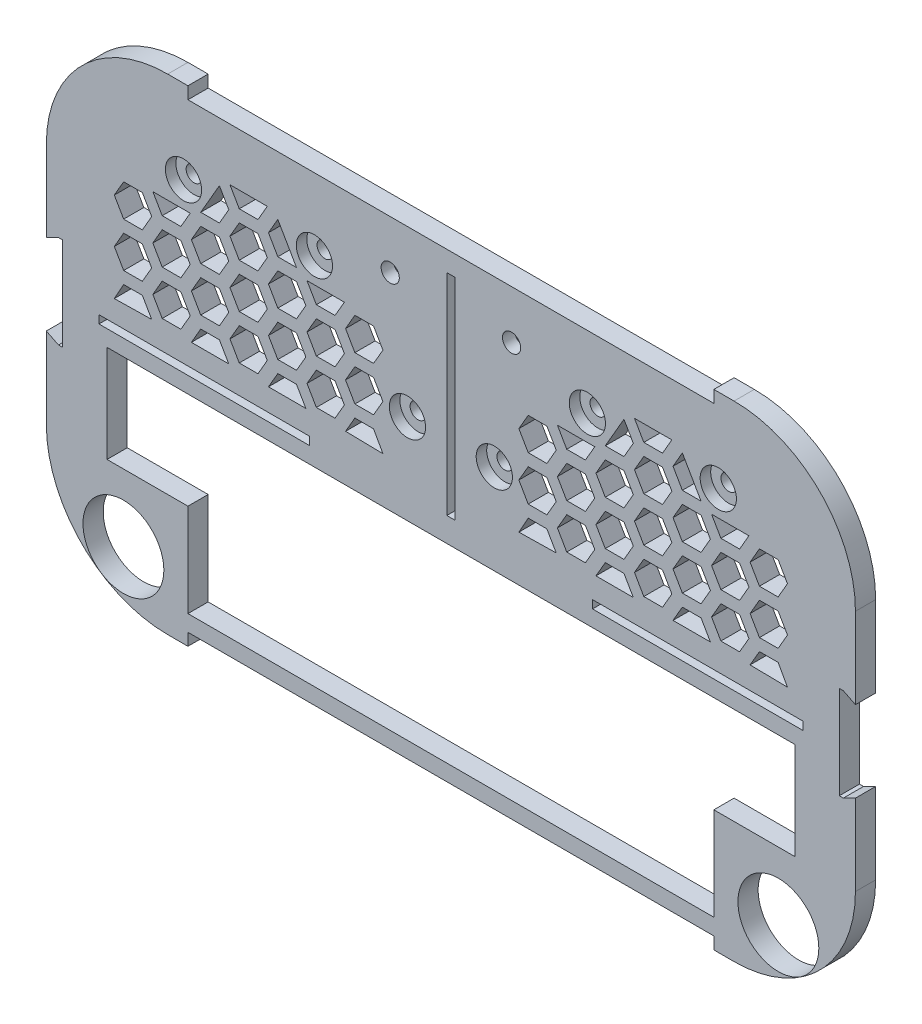
SolidWorks part; units mm, degrees
ref_plane "前视基准面" through (0, 0, 0) normal (0, 0, 1) x (1, 0, 0)
ref_plane "上视基准面" through (0, 0, 0) normal (0, 1, 0) x (1, 0, 0)
ref_plane "右视基准面" through (0, 0, 0) normal (1, 0, 0) x (0, 0, -1)
sketch "草图1" plane through (0, 0, 0) normal (0, 0, 1) x (1, 0, 0)
  line L1 (70, 60) -> (-70, 60)
  line L2 (-100, 30) -> (-100, -30)
  line L4 (70, -60) -> (-70, -60)
  line L5 (100, 30) -> (100, -30)
  arc A0 (-70, 60) -> (-100, 30) centre (-70, 30) ccw
  arc A1 (-70, -60) -> (-100, -30) centre (-70, -30) cw
  arc A2 (70, -60) -> (100, -30) centre (70, -30) ccw
  arc A3 (70, 60) -> (100, 30) centre (70, 30) cw
  point P12 (0, -60)
extrude "凸台-拉伸1" add sketch "草图1" along normal blind 5
sketch "草图2" plane through (0, 0, 0) normal (0, 0, 1) x (1, 0, 0)
  circle A0 centre (-80.95, 46.6721) radius 10
  circle A1 centre (80.95, 46.6721) radius 10
  circle A2 centre (80.95, -46.6721) radius 10
  circle A3 centre (-80.95, -46.6721) radius 10
extrude "孔" cut sketch "草图2" along normal blind 4 contours A1 | A0 region at (-80.95, 46.6721, 0) region at (80.95, 46.6721, 0)
extrude "穿孔" cut sketch "草图2<3>" along normal up to next contours A2 | A3 region at (80.95, -46.6721, 0) region at (-80.95, -46.6721, 0)
sketch "草图2<3>" plane through (0, 0, 0) normal (0, 0, 1) x (1, 0, 0) same geometry as "草图2"
sketch "草图3" plane through (0, 0, 0) normal (0, 0, 1) x (1, 0, 0)
  line L8 (-85, -6) -> (-85, -30)
  line L12 (-70, -30) -> (-65, -30)
  line L22 (-85, -30) -> (-70, -30)
  line L26 (85, -30) -> (70, -30)
  line L32 (70, -30) -> (65, -30)
  line L37 (-65, -30) -> (-65, -53)
  line L39 (65, -53) -> (65, -30)
  line L40 (-65, -60) -> (-65, -57)
  line L41 (-70, -60) -> (70, -60) construction
  line L42 (-65, -57) -> (65, -57)
  line L43 (65, -57) -> (65, -60)
  line L44 (-65, -60) -> (65, -60)
  line L50 (-100, -10) -> (-97, -11.5)
  line L53 (-100, 10) -> (-100, -10)
  line L55 (-85, -6) -> (85, -6)
  line L56 (85, -6) -> (85, -30)
  line L88 (65, -53) -> (-65, -53)
  line L89 (87, 0) -> (87, -2)
  line L90 (87, -2) -> (35, -2)
  line L92 (87, 0) -> (37, 0)
  line L96 (35, 0) -> (35, -2)
  line L105 (-35, 0) -> (-35, -2)
  line L109 (-87, 0) -> (-37, 0)
  line L110 (-87, -2) -> (-35, -2)
  line L111 (-87, 0) -> (-87, -2)
  line L112 (97, 11.5) -> (96, 11.5)
  line L114 (-97, 11.5) -> (-100, 10)
  line L115 (97, 11.5) -> (100, 10)
  line L118 (100, 10) -> (100, -10)
  line L119 (100, -10) -> (97, -11.5)
  line L120 (96, 11.5) -> (96, -11.5)
  line L121 (96, -11.5) -> (97, -11.5)
  line L122 (-97, 11.5) -> (-96, 11.5)
  line L123 (-96, 11.5) -> (-96, -11.5)
  line L124 (-96, -11.5) -> (-97, -11.5)
  line L125 (0, 0) -> (-1, 0)
  line L126 (-1, 0) -> (-1, 50)
  line L128 (1, 50) -> (1, 0)
  line L129 (1, 0) -> (0, 0)
  line L130 (-1, 50) -> (-1, 52)
  line L131 (-1, 52) -> (1, 52)
  line L132 (1, 52) -> (1, 50)
  line L133 (-37, 0) -> (-35, 0)
  line L134 (35, 0) -> (37, 0)
  line L135 (-65, 57) -> (-65, 60)
  line L136 (-65, 57) -> (65, 57)
  line L138 (65, 57) -> (65, 60)
  line L139 (65, 60) -> (-65, 60)
extrude "切除-拉伸4" cut sketch "草图3" along normal up to next
hole_wizard "M3.5 六角头机械螺钉的柱形沉头孔1" positions "3D草图1" profile "草图4" counterbore size "M3.5" standard "ANSI Metric" end condition through all
sketch3d "3D草图1"
  point P31 (-66.0951, 39.3344, 5)
  point P33 (-33.736, 39.2649, 5)
  point P35 (-10.7334, 16.264, 5)
  point P78 (33.736, 39.2649, 5)
  point P80 (10.7334, 16.264, 5)
  point P82 (66.0951, 39.3344, 5)
sketch "草图4" plane through (-66.0951, 39.3344, 5) normal (1, 0, 0) x (0, -1, 0)
  line L0 (0, 0) -> (0, 5)
  line L1 (0, 5) -> (1.95, 5)
  line L3 (1.95, 5) -> (1.95, 2.6)
  line L4 (1.95, 2.6) -> (4.48, 2.6)
  line L5 (4.48, 2.6) -> (4.48, 0)
  line L7 (4.48, 0) -> (0, 0)
  line L11 (0, -6.35) -> (0, 107.95) construction
  dimension "通孔孔直径" = 3.9
  dimension "通孔孔深度" = 5
  dimension "柱形沉头孔直径" = 8.96
  dimension "柱形沉头孔深度" = 2.6
sketch "草图5" plane through (0, 0, 0) normal (0, 0, 1) x (1, 0, 0)
  line L4 (-35.8549, 5.5) -> (-38.1643, 9.5)
  line L6 (-38.1643, 9.5) -> (-42.7831, 9.5)
  line L13 (-42.7831, 9.5) -> (-45.0925, 5.5)
  line L17 (-26.3286, 11) -> (-28.638, 15)
  line L18 (-28.638, 15) -> (-33.2568, 15)
  line L19 (-33.2568, 15) -> (-35.5662, 11)
  line L20 (-35.5662, 11) -> (-33.2568, 7)
  line L21 (-33.2568, 7) -> (-28.638, 7)
  line L22 (-28.638, 7) -> (-26.3286, 11)
  line L23 (-16.8024, 16.5) -> (-19.1118, 20.5)
  line L24 (-19.1118, 20.5) -> (-23.7306, 20.5)
  line L25 (-23.7306, 20.5) -> (-26.04, 16.5)
  line L26 (-26.04, 16.5) -> (-23.7306, 12.5)
  line L27 (-23.7306, 12.5) -> (-19.1118, 12.5)
  line L28 (-19.1118, 12.5) -> (-16.8024, 16.5)
  line L29 (-35.8549, 16.5) -> (-38.1643, 20.5)
  line L30 (-38.1643, 20.5) -> (-42.7831, 20.5)
  line L31 (-42.7831, 20.5) -> (-45.0925, 16.5)
  line L32 (-45.0925, 16.5) -> (-42.7831, 12.5)
  line L33 (-42.7831, 12.5) -> (-38.1643, 12.5)
  line L34 (-38.1643, 12.5) -> (-35.8549, 16.5)
  line L35 (-26.3286, 22) -> (-28.638, 26)
  line L36 (-28.638, 26) -> (-33.2568, 26)
  line L37 (-33.2568, 26) -> (-35.5662, 22)
  line L38 (-35.5662, 22) -> (-33.2568, 18)
  line L39 (-33.2568, 18) -> (-28.638, 18)
  line L40 (-28.638, 18) -> (-26.3286, 22)
  line L41 (-16.8024, 27.5) -> (-19.1118, 31.5)
  line L42 (-19.1118, 31.5) -> (-23.7306, 31.5)
  line L43 (-23.7306, 31.5) -> (-26.04, 27.5)
  line L44 (-26.04, 27.5) -> (-23.7306, 23.5)
  line L45 (-23.7306, 23.5) -> (-19.1118, 23.5)
  line L46 (-19.1118, 23.5) -> (-16.8024, 27.5)
  line L47 (-35.8549, 27.5) -> (-38.1643, 31.5)
  line L48 (-38.1643, 31.5) -> (-42.7831, 31.5)
  line L49 (-42.7831, 31.5) -> (-45.0925, 27.5)
  line L50 (-45.0925, 27.5) -> (-42.7831, 23.5)
  line L51 (-42.7831, 23.5) -> (-38.1643, 23.5)
  line L52 (-38.1643, 23.5) -> (-35.8549, 27.5)
  line L56 (-35.5662, 33) -> (-33.2568, 29)
  line L57 (-33.2568, 29) -> (-28.638, 29)
  line L58 (-28.638, 29) -> (-26.3286, 33)
  line L67 (-42.7831, 42.5) -> (-45.0925, 38.5)
  line L68 (-45.0925, 38.5) -> (-42.7831, 34.5)
  line L69 (-42.7831, 34.5) -> (-38.1643, 34.5)
  line L83 (-45.3812, 11) -> (-47.6906, 15)
  line L84 (-47.6906, 15) -> (-52.3094, 15)
  line L85 (-52.3094, 15) -> (-54.6188, 11)
  line L86 (-54.6188, 11) -> (-52.3094, 7)
  line L87 (-52.3094, 7) -> (-47.6906, 7)
  line L88 (-47.6906, 7) -> (-45.3812, 11)
  line L89 (-45.3812, 22) -> (-47.6906, 26)
  line L90 (-47.6906, 26) -> (-52.3094, 26)
  line L91 (-52.3094, 26) -> (-54.6188, 22)
  line L92 (-54.6188, 22) -> (-52.3094, 18)
  line L93 (-52.3094, 18) -> (-47.6906, 18)
  line L94 (-47.6906, 18) -> (-45.3812, 22)
  line L95 (-45.3812, 33) -> (-47.6906, 37)
  line L96 (-47.6906, 37) -> (-52.3094, 37)
  line L97 (-52.3094, 37) -> (-54.6188, 33)
  line L98 (-54.6188, 33) -> (-52.3094, 29)
  line L99 (-52.3094, 29) -> (-47.6906, 29)
  line L100 (-47.6906, 29) -> (-45.3812, 33)
  line L125 (-42.7831, 42.5) -> (-38.1643, 34.5)
  line L126 (-35.5662, 33) -> (-26.3286, 33)
  line L127 (-45.0925, 5.5) -> (-35.8549, 5.5)
  line L129 (-54.9075, 5.5) -> (-64.1451, 5.5)
  line L130 (-64.4338, 33) -> (-73.6714, 33)
  line L131 (-57.2169, 42.5) -> (-61.8357, 34.5)
  line L132 (-57.2169, 34.5) -> (-61.8357, 34.5)
  line L133 (-54.9075, 38.5) -> (-57.2169, 34.5)
  line L134 (-57.2169, 42.5) -> (-54.9075, 38.5)
  line L135 (-71.362, 29) -> (-73.6714, 33)
  line L136 (-66.7432, 29) -> (-71.362, 29)
  line L137 (-64.4338, 33) -> (-66.7432, 29)
  line L138 (-61.8357, 23.5) -> (-64.1451, 27.5)
  line L139 (-57.2169, 23.5) -> (-61.8357, 23.5)
  line L140 (-54.9075, 27.5) -> (-57.2169, 23.5)
  line L141 (-57.2169, 31.5) -> (-54.9075, 27.5)
  line L142 (-61.8357, 31.5) -> (-57.2169, 31.5)
  line L143 (-64.1451, 27.5) -> (-61.8357, 31.5)
  line L144 (-80.8882, 23.5) -> (-83.1976, 27.5)
  line L145 (-76.2694, 23.5) -> (-80.8882, 23.5)
  line L146 (-73.96, 27.5) -> (-76.2694, 23.5)
  line L147 (-76.2694, 31.5) -> (-73.96, 27.5)
  line L148 (-80.8882, 31.5) -> (-76.2694, 31.5)
  line L149 (-83.1976, 27.5) -> (-80.8882, 31.5)
  line L150 (-71.362, 18) -> (-73.6714, 22)
  line L151 (-66.7432, 18) -> (-71.362, 18)
  line L152 (-64.4338, 22) -> (-66.7432, 18)
  line L153 (-66.7432, 26) -> (-64.4338, 22)
  line L154 (-71.362, 26) -> (-66.7432, 26)
  line L155 (-73.6714, 22) -> (-71.362, 26)
  line L156 (-61.8357, 12.5) -> (-64.1451, 16.5)
  line L157 (-57.2169, 12.5) -> (-61.8357, 12.5)
  line L158 (-54.9075, 16.5) -> (-57.2169, 12.5)
  line L159 (-57.2169, 20.5) -> (-54.9075, 16.5)
  line L160 (-61.8357, 20.5) -> (-57.2169, 20.5)
  line L161 (-64.1451, 16.5) -> (-61.8357, 20.5)
  line L162 (-80.8882, 12.5) -> (-83.1976, 16.5)
  line L163 (-76.2694, 12.5) -> (-80.8882, 12.5)
  line L164 (-73.96, 16.5) -> (-76.2694, 12.5)
  line L165 (-76.2694, 20.5) -> (-73.96, 16.5)
  line L166 (-80.8882, 20.5) -> (-76.2694, 20.5)
  line L167 (-83.1976, 16.5) -> (-80.8882, 20.5)
  line L168 (-71.362, 7) -> (-73.6714, 11)
  line L169 (-66.7432, 7) -> (-71.362, 7)
  line L170 (-64.4338, 11) -> (-66.7432, 7)
  line L171 (-66.7432, 15) -> (-64.4338, 11)
  line L172 (-71.362, 15) -> (-66.7432, 15)
  line L173 (-73.6714, 11) -> (-71.362, 15)
  line L174 (-57.2169, 9.5) -> (-54.9075, 5.5)
  line L175 (-61.8357, 9.5) -> (-57.2169, 9.5)
  line L176 (-64.1451, 5.5) -> (-61.8357, 9.5)
  line L181 (-52.3094, 40) -> (-47.6906, 40)
  line L184 (-52.3094, 44) -> (-54.6188, 44)
  line L185 (-54.6188, 44) -> (-52.3094, 40)
  line L186 (-52.3094, 44) -> (-45.3812, 44)
  line L187 (-45.3812, 44) -> (-47.6906, 40)
  line L188 (-21.4212, 9.5) -> (-23.7306, 9.5)
  line L191 (-26.04, 5.5) -> (-23.7306, 9.5)
  line L192 (-26.04, 5.5) -> (-16.8024, 5.3417)
  line L193 (-16.8024, 5.3417) -> (-19.1118, 9.5)
  line L194 (-19.1118, 9.5) -> (-21.4212, 9.5)
  line L195 (-80.8882, 9.5) -> (-78.5788, 9.5)
  line L196 (-83.1976, 5.3417) -> (-80.8882, 9.5)
  line L197 (-73.96, 5.5) -> (-83.1976, 5.3417)
  line L198 (-73.96, 5.5) -> (-76.2694, 9.5)
  line L199 (-78.5788, 9.5) -> (-76.2694, 9.5)
  line L200 (78.5788, 9.5) -> (76.2694, 9.5)
  line L201 (73.96, 5.5) -> (76.2694, 9.5)
  line L202 (73.96, 5.5) -> (83.1976, 5.3417)
  line L203 (83.1976, 5.3417) -> (80.8882, 9.5)
  line L204 (80.8882, 9.5) -> (78.5788, 9.5)
  line L205 (19.1118, 9.5) -> (21.4212, 9.5)
  line L206 (16.8024, 5.3417) -> (19.1118, 9.5)
  line L207 (26.04, 5.5) -> (16.8024, 5.3417)
  line L208 (26.04, 5.5) -> (23.7306, 9.5)
  line L209 (21.4212, 9.5) -> (23.7306, 9.5)
  line L210 (45.3812, 44) -> (47.6906, 40)
  line L211 (52.3094, 44) -> (45.3812, 44)
  line L212 (54.6188, 44) -> (52.3094, 40)
  line L213 (52.3094, 44) -> (54.6188, 44)
  line L214 (52.3094, 40) -> (47.6906, 40)
  line L215 (64.1451, 5.5) -> (61.8357, 9.5)
  line L216 (61.8357, 9.5) -> (57.2169, 9.5)
  line L217 (57.2169, 9.5) -> (54.9075, 5.5)
  line L218 (73.6714, 11) -> (71.362, 15)
  line L219 (71.362, 15) -> (66.7432, 15)
  line L220 (66.7432, 15) -> (64.4338, 11)
  line L221 (64.4338, 11) -> (66.7432, 7)
  line L222 (66.7432, 7) -> (71.362, 7)
  line L223 (71.362, 7) -> (73.6714, 11)
  line L224 (83.1976, 16.5) -> (80.8882, 20.5)
  line L225 (80.8882, 20.5) -> (76.2694, 20.5)
  line L226 (76.2694, 20.5) -> (73.96, 16.5)
  line L227 (73.96, 16.5) -> (76.2694, 12.5)
  line L228 (76.2694, 12.5) -> (80.8882, 12.5)
  line L229 (80.8882, 12.5) -> (83.1976, 16.5)
  line L230 (64.1451, 16.5) -> (61.8357, 20.5)
  line L231 (61.8357, 20.5) -> (57.2169, 20.5)
  line L232 (57.2169, 20.5) -> (54.9075, 16.5)
  line L233 (54.9075, 16.5) -> (57.2169, 12.5)
  line L234 (57.2169, 12.5) -> (61.8357, 12.5)
  line L235 (61.8357, 12.5) -> (64.1451, 16.5)
  line L236 (73.6714, 22) -> (71.362, 26)
  line L237 (71.362, 26) -> (66.7432, 26)
  line L238 (66.7432, 26) -> (64.4338, 22)
  line L239 (64.4338, 22) -> (66.7432, 18)
  line L240 (66.7432, 18) -> (71.362, 18)
  line L241 (71.362, 18) -> (73.6714, 22)
  line L242 (83.1976, 27.5) -> (80.8882, 31.5)
  line L243 (80.8882, 31.5) -> (76.2694, 31.5)
  line L244 (76.2694, 31.5) -> (73.96, 27.5)
  line L245 (73.96, 27.5) -> (76.2694, 23.5)
  line L246 (76.2694, 23.5) -> (80.8882, 23.5)
  line L247 (80.8882, 23.5) -> (83.1976, 27.5)
  line L248 (64.1451, 27.5) -> (61.8357, 31.5)
  line L249 (61.8357, 31.5) -> (57.2169, 31.5)
  line L250 (57.2169, 31.5) -> (54.9075, 27.5)
  line L251 (54.9075, 27.5) -> (57.2169, 23.5)
  line L252 (57.2169, 23.5) -> (61.8357, 23.5)
  line L253 (61.8357, 23.5) -> (64.1451, 27.5)
  line L254 (64.4338, 33) -> (66.7432, 29)
  line L255 (66.7432, 29) -> (71.362, 29)
  line L256 (71.362, 29) -> (73.6714, 33)
  line L257 (57.2169, 42.5) -> (54.9075, 38.5)
  line L258 (54.9075, 38.5) -> (57.2169, 34.5)
  line L259 (57.2169, 34.5) -> (61.8357, 34.5)
  line L260 (57.2169, 42.5) -> (61.8357, 34.5)
  line L261 (64.4338, 33) -> (73.6714, 33)
  line L262 (54.9075, 5.5) -> (64.1451, 5.5)
  line L263 (45.0925, 5.5) -> (35.8549, 5.5)
  line L264 (35.5662, 33) -> (26.3286, 33)
  line L265 (42.7831, 42.5) -> (38.1643, 34.5)
  line L266 (47.6906, 29) -> (45.3812, 33)
  line L267 (52.3094, 29) -> (47.6906, 29)
  line L268 (54.6188, 33) -> (52.3094, 29)
  line L269 (52.3094, 37) -> (54.6188, 33)
  line L270 (47.6906, 37) -> (52.3094, 37)
  line L271 (45.3812, 33) -> (47.6906, 37)
  line L272 (47.6906, 18) -> (45.3812, 22)
  line L273 (52.3094, 18) -> (47.6906, 18)
  line L274 (54.6188, 22) -> (52.3094, 18)
  line L275 (52.3094, 26) -> (54.6188, 22)
  line L276 (47.6906, 26) -> (52.3094, 26)
  line L277 (45.3812, 22) -> (47.6906, 26)
  line L278 (47.6906, 7) -> (45.3812, 11)
  line L279 (52.3094, 7) -> (47.6906, 7)
  line L280 (54.6188, 11) -> (52.3094, 7)
  line L281 (52.3094, 15) -> (54.6188, 11)
  line L282 (47.6906, 15) -> (52.3094, 15)
  line L283 (45.3812, 11) -> (47.6906, 15)
  line L284 (42.7831, 34.5) -> (38.1643, 34.5)
  line L285 (45.0925, 38.5) -> (42.7831, 34.5)
  line L286 (42.7831, 42.5) -> (45.0925, 38.5)
  line L287 (28.638, 29) -> (26.3286, 33)
  line L288 (33.2568, 29) -> (28.638, 29)
  line L289 (35.5662, 33) -> (33.2568, 29)
  line L290 (38.1643, 23.5) -> (35.8549, 27.5)
  line L291 (42.7831, 23.5) -> (38.1643, 23.5)
  line L292 (45.0925, 27.5) -> (42.7831, 23.5)
  line L293 (42.7831, 31.5) -> (45.0925, 27.5)
  line L294 (38.1643, 31.5) -> (42.7831, 31.5)
  line L295 (35.8549, 27.5) -> (38.1643, 31.5)
  line L296 (19.1118, 23.5) -> (16.8024, 27.5)
  line L297 (23.7306, 23.5) -> (19.1118, 23.5)
  line L298 (26.04, 27.5) -> (23.7306, 23.5)
  line L299 (23.7306, 31.5) -> (26.04, 27.5)
  line L300 (19.1118, 31.5) -> (23.7306, 31.5)
  line L301 (16.8024, 27.5) -> (19.1118, 31.5)
  line L302 (28.638, 18) -> (26.3286, 22)
  line L303 (33.2568, 18) -> (28.638, 18)
  line L304 (35.5662, 22) -> (33.2568, 18)
  line L305 (33.2568, 26) -> (35.5662, 22)
  line L306 (28.638, 26) -> (33.2568, 26)
  line L307 (26.3286, 22) -> (28.638, 26)
  line L308 (38.1643, 12.5) -> (35.8549, 16.5)
  line L309 (42.7831, 12.5) -> (38.1643, 12.5)
  line L310 (45.0925, 16.5) -> (42.7831, 12.5)
  line L311 (42.7831, 20.5) -> (45.0925, 16.5)
  line L312 (38.1643, 20.5) -> (42.7831, 20.5)
  line L313 (35.8549, 16.5) -> (38.1643, 20.5)
  line L314 (19.1118, 12.5) -> (16.8024, 16.5)
  line L315 (23.7306, 12.5) -> (19.1118, 12.5)
  line L316 (26.04, 16.5) -> (23.7306, 12.5)
  line L317 (23.7306, 20.5) -> (26.04, 16.5)
  line L318 (19.1118, 20.5) -> (23.7306, 20.5)
  line L319 (16.8024, 16.5) -> (19.1118, 20.5)
  line L320 (28.638, 7) -> (26.3286, 11)
  line L321 (33.2568, 7) -> (28.638, 7)
  line L322 (35.5662, 11) -> (33.2568, 7)
  line L323 (33.2568, 15) -> (35.5662, 11)
  line L324 (28.638, 15) -> (33.2568, 15)
  line L325 (26.3286, 11) -> (28.638, 15)
  line L326 (42.7831, 9.5) -> (45.0925, 5.5)
  line L327 (38.1643, 9.5) -> (42.7831, 9.5)
  line L328 (35.8549, 5.5) -> (38.1643, 9.5)
extrude "切除-拉伸5" cut sketch "草图5" against normal through all and the other way through all
ref_plane "基准面1" through (0, 0, 0) normal (0, 0, -1) x (-1, 0, 0)
sketch "草图8" plane through (0, 0, 0) normal (0, 0, 1) x (1, 0, 0)
  line L0 (-6, 22) -> (-1, 22)
  line L5 (-26, 52) -> (-26, 47)
  line L7 (-24, 47) -> (-24, 52)
  line L8 (-26, 47) -> (-66, 47)
  line L9 (-66, 47) -> (-66, 52)
  line L10 (-66, 52) -> (-26, 52)
  line L18 (-1, 22) -> (-1, 52)
  line L20 (-24, 52) -> (-1, 52)
  line L42 (24, 47) -> (6, 22)
  line L43 (-24, 47) -> (-6, 22)
  line L44 (24, 52) -> (1, 52)
  line L45 (1, 22) -> (1, 52)
  line L46 (66, 52) -> (26, 52)
  line L47 (66, 47) -> (66, 52)
  line L48 (26, 47) -> (66, 47)
  line L49 (24, 47) -> (24, 52)
  line L50 (26, 52) -> (26, 47)
  line L51 (6, 22) -> (1, 22)
  circle A6 centre (15, 45) radius 5
  circle A7 centre (-15, 45) radius 5
extrude "切除-拉伸7" cut sketch "草图8" along normal blind 3
hole_wizard "M4 六角凹头盖的柱孔1" positions "3D草图4" profile "草图11" counterbore size "M4" standard "BSI" end condition through all
sketch3d "3D草图4"
  line L5 (15, 45, 3) -> (-15, 45, 3)
  line L6 (15, 45, 3) -> (15, 45, 0) construction
  line L7 (-15, 45, 3) -> (-15, 45, 0) construction
  point P17 (15, 45, 0)
  point P19 (-15, 45, 0)
sketch "草图11" plane through (-15, 45, 0) normal (1, 0, 0) x (0, 1, 0)
  line L0 (0, 0) -> (0, 5)
  line L1 (0, 5) -> (2.25, 5)
  line L3 (2.25, 5) -> (2.25, 2)
  line L4 (2.25, 2) -> (4, 2)
  line L5 (4, 2) -> (4, 0)
  line L7 (4, 0) -> (0, 0)
  line L11 (0, -6.35) -> (0, 107.95) construction
  dimension "通孔孔直径" = 4.5
  dimension "通孔孔深度" = 5
  dimension "柱形沉头孔直径" = 8
  dimension "柱形沉头孔深度" = 2
